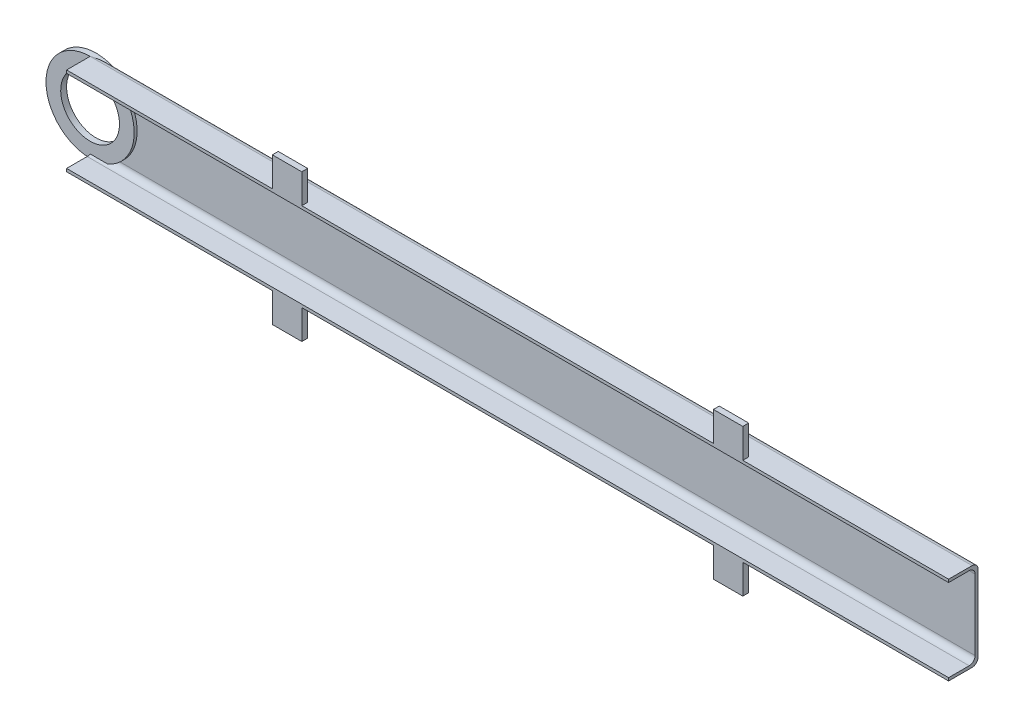
SolidWorks part; units mm, degrees
ref_plane "Front Plane" through (0, 0, 0) normal (0, 0, 1) x (1, 0, 0)
ref_plane "Top Plane" through (0, 0, 0) normal (0, 1, 0) x (1, 0, 0)
ref_plane "Right Plane" through (0, 0, 0) normal (1, 0, 0) x (0, 0, -1)
sketch "Sketch1" plane through (0, 0, 0) normal (1, 0, 0) x (0, 0, -1)
  line L0 (0, 0) -> (0, 16.6254) construction
  line L1 (0, 16.6254) -> (0, -20.4032) construction
  line L2 (0, 0) -> (27.0278, 0) construction
  line L3 (0, 15) -> (8, 15)
  line L4 (10, 13) -> (10, -13)
  line L5 (8, -15) -> (0, -15)
  line L6 (0, -15) -> (0, -14)
  line L7 (0, -14) -> (7, -14)
  line L8 (9, -12) -> (9, 12)
  line L9 (7, 14) -> (0, 14)
  line L10 (0, 15) -> (0, 14)
  line L11 (0, -14) -> (0, -15)
  line L12 (0, 15) -> (0, 14)
  line L13 (0, -14) -> (0, -15)
  arc A0 (8, -15) -> (10, -13) centre (8, -13) ccw
  arc A1 (7, -14) -> (9, -12) centre (7, -12) ccw
  arc A2 (9, 12) -> (7, 14) centre (7, 12) ccw
  arc A3 (10, 13) -> (8, 15) centre (8, 13) ccw
  point P3 (9, 0)
  point P6 (10, 0)
  point P7 (0, 15)
  point P8 (0, 14)
  point P9 (0, -14)
  point P10 (0, -15)
  point P23 (10, -15)
  point P26 (9, -14)
  dimension "D7" = 2
  dimension "D1" = 10
  dimension "D2" = 9
  dimension "D3" = 15
  dimension "D4" = 15
  dimension "D5" = 14
  dimension "D6" = 14
extrude "Boss-Extrude1" add sketch "Sketch1" along normal blind 300 contours L4 A3 L3 L10 L9 A2 L8 A1 L7 L6 L5 A0 region at (0, 14.6838, -4)
ref_plane "Plane1" through (0, 0, 0) normal (0, 0, 1) x (1, 0, 0)
sketch "Sketch2" plane through (0, 0, 0) normal (0, 0, 1) x (1, 0, 0)
  line L0 (0, 0) -> (407.5111, 0) construction
  line L1 (75, 43.9173) -> (75, -52.4948) construction
  line L2 (225, 0) -> (225, 43.9173) construction
  line L3 (225, 43.9173) -> (225, -52.4948) construction
  line L4 (300, -12) -> (300, 12) construction
  line L5 (300, 15) -> (0, 15) construction
  line L6 (70, 25) -> (80, 25)
  line L7 (70, 25) -> (70, 15)
  line L8 (70, 15) -> (80, 15)
  line L9 (80, 25) -> (80, 15)
  line L10 (70, 25) -> (80, 15) construction
  line L11 (70, 15) -> (80, 25) construction
  line L12 (300, -15) -> (0, -15) construction
  line L13 (70, -25) -> (80, -25)
  line L14 (70, -25) -> (70, -15)
  line L15 (70, -15) -> (80, -15)
  line L16 (80, -25) -> (80, -15)
  line L17 (70, -25) -> (80, -15) construction
  line L18 (70, -15) -> (80, -25) construction
  line L20 (230, 25) -> (220, 25)
  line L21 (230, 25) -> (230, 15)
  line L22 (230, 15) -> (220, 15)
  line L23 (220, 25) -> (220, 15)
  line L24 (230, 25) -> (220, 15) construction
  line L25 (230, 15) -> (220, 25) construction
  line L26 (230, -25) -> (220, -25)
  line L27 (230, -25) -> (230, -15)
  line L28 (230, -15) -> (220, -15)
  line L29 (220, -25) -> (220, -15)
  line L30 (230, -25) -> (220, -15) construction
  line L31 (230, -15) -> (220, -25) construction
  point P3 (75, 0)
  point P4 (225, 0)
  point P10 (75, 20)
  point P11 (300, 0)
  point P12 (75, -20)
  point P15 (225, 20)
  point P16 (225, -20)
  point P19 (75, 20)
  point P24 (75, -20)
  point P31 (225, 20)
  point P36 (225, -20)
  point P41 (0, 0)
  point P42 (216.9815, -15)
  point P43 (81.9822, -15)
  point P44 (0, 0)
  point P45 (0, 0)
  dimension "D1" = 75
  dimension "D2" = 75
  dimension "D3" = 20
  dimension "D4" = 20
  dimension "D5" = 10
  dimension "D6" = 10
extrude "Boss-Extrude2" add sketch "Sketch2" against normal blind 2
ref_plane "Plane2" through (0, 0, -10) normal (0, 0, -1) x (-1, 0, 0)
sketch "Sketch4" plane through (0, 0, -10) normal (0, 0, -1) x (-1, 0, 0)
  circle A0 centre (0, 0) radius 15
  circle A1 centre (0, 0) radius 10
  circle A2 centre (0, 0) radius 14
  dimension "D1" = 20
  dimension "D2" = 28
extrude "Boss-Extrude3" add sketch "Sketch4" against normal blind 2 contours A0 A2 | A2 A1 region at (14.5757, 0, -10) region at (13.604, 0, -10)
extrude "Cut-Extrude1" cut sketch "Sketch4<3>" against normal blind 2 contours A1 region at (0, 0, -10)
sketch "Sketch4<3>" plane through (0, 0, -10) normal (0, 0, -1) x (-1, 0, 0) same geometry as "Sketch4"
